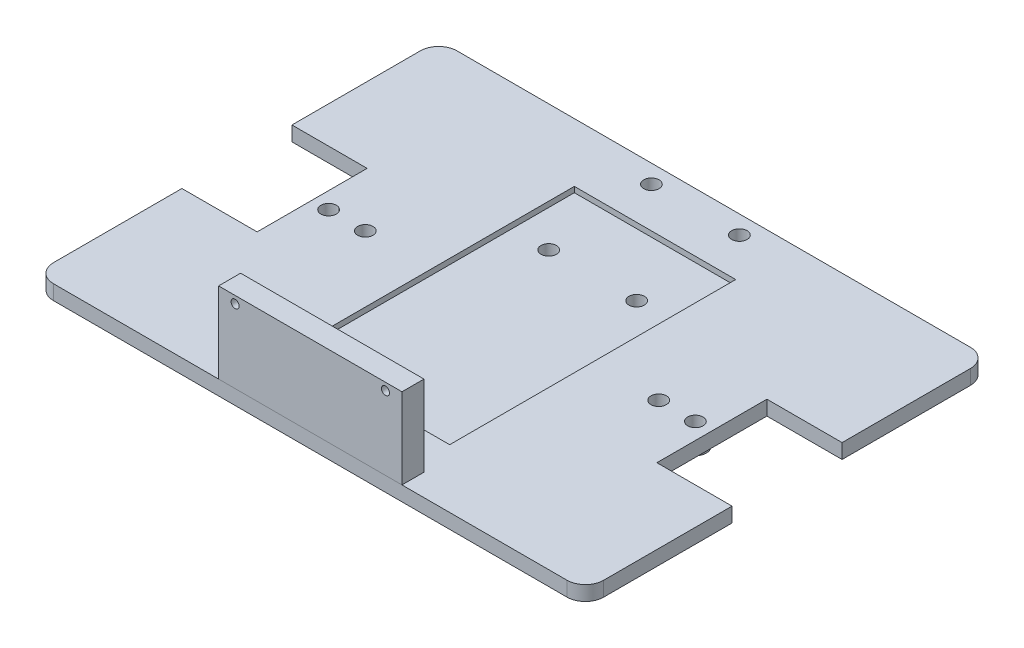
SolidWorks part; units mm, degrees
ref_plane "Front Plane" through (0, 0, 0) normal (0, 0, 1) x (1, 0, 0)
ref_plane "Top Plane" through (0, 0, 0) normal (0, 1, 0) x (1, 0, 0)
ref_plane "Right Plane" through (0, 0, 0) normal (1, 0, 0) x (0, 0, -1)
sketch "Sketch1" plane through (0, 0, 0) normal (0, 1, 0) x (1, 0, 0)
  line L0 (-75, 0) -> (75, 0) construction
  line L1 (-75, -55) -> (75, -55)
  line L2 (-75, -55) -> (-75, 55)
  line L3 (-75, 55) -> (75, 55)
  line L4 (75, -55) -> (75, 55)
  line L5 (-75, -55) -> (75, 55) construction
  line L6 (-75, 55) -> (75, -55) construction
  point P0 (0, 0)
  dimension "D1" = 150
  dimension "D2" = 110
extrude "Boss-Extrude1" add sketch "Sketch1" along normal blind 4
fillet "Fillet1" radius 5 4 edges at (-75, 2, -55) (-75, 2, 55) (75, 2, -55) (75, 2, 55)
sketch "Sketch2" plane through (0, 4, 0) normal (0, 1, 0) x (1, 0, 0)
  line L0 (-75, 0) -> (75, 0) construction
  line L1 (-75, 50) -> (-75, -50) construction
  line L2 (75, -50) -> (75, 50) construction
  line L3 (0, 55) -> (0, -55) construction
  line L4 (70, 55) -> (-70, 55) construction
  line L5 (-70, -55) -> (70, -55) construction
  circle A0 centre (-50, 0) radius 2.1
  circle A1 centre (-40, 0) radius 2.1
  dimension "D1" = 4.2
  dimension "D2" = 50
  dimension "D3" = 4.2
  dimension "D4" = 40
extrude "Cut-Extrude1" cut sketch "Sketch2" against normal through all
sketch "Sketch3" plane through (0, 0, 0) normal (0, -1, 0) x (1, 0, 0)
  line L0 (-75, 0) -> (75, 0) construction
  line L1 (-75, -50) -> (-75, 50) construction
  line L2 (75, 50) -> (75, -50) construction
  line L3 (0, 55) -> (0, -55) construction
  line L4 (-70, 55) -> (70, 55) construction
  line L5 (70, -55) -> (-70, -55) construction
  circle A0 centre (-50, 0) radius 3
  circle A1 centre (-40, 0) radius 3
  dimension "D1" = 6
  dimension "D2" = 6
extrude "Boss-Extrude2" add sketch "Sketch3" along normal blind 2
mirror "Mirror1" about plane through (0, 0, 0) normal (1, 0, 0) of "Boss-Extrude2", "Cut-Extrude1"
sketch "Sketch4" plane through (0, 4, 0) normal (0, 1, 0) x (1, 0, 0)
  line L0 (0, -55) -> (0, 55) construction
  line L1 (-22, -39) -> (-6, -39)
  line L2 (-22, -39) -> (-22, 39)
  line L3 (-22, 39) -> (22, 39)
  line L4 (22, -39) -> (22, 39)
  line L5 (-22, -39) -> (22, 39) construction
  line L6 (-22, 39) -> (22, -39) construction
  line L7 (-70, -55) -> (70, -55) construction
  line L8 (70, 55) -> (-70, 55) construction
  line L9 (6, -39) -> (22, -39)
  line L10 (-6, -43) -> (6, -43)
  line L11 (-6, -43) -> (-6, -39)
  line L13 (6, -43) -> (6, -39)
  line L14 (-6, -43) -> (6, -39) construction
  line L15 (-6, -39) -> (6, -43) construction
  point P0 (0, 0)
  point P15 (0, -41)
  dimension "D1" = 44
  dimension "D2" = 78
  dimension "D3" = 0
  dimension "D4" = 4
  dimension "D5" = 12
extrude "Cut-Extrude2" cut sketch "Sketch4" against normal blind 1.5
sketch "Sketch7" plane through (0, 0, 55) normal (0, 0, 1) x (1, 0, 0)
  line L0 (-70, 4) -> (70, 4) construction
  line L1 (-25, 4) -> (25, 4)
  line L2 (-25, 4) -> (-25, 26)
  line L3 (-25, 26) -> (25, 26)
  line L4 (25, 4) -> (25, 26)
  line L5 (-25, 4) -> (25, 26) construction
  line L6 (-25, 26) -> (25, 4) construction
  line L7 (70, 0) -> (70, 4) construction
  point P0 (0, 4)
  point P10 (0, 26)
  dimension "D1" = 50
  dimension "D2" = 22
  dimension "D3" = 45
extrude "Boss-Extrude4" add sketch "Sketch7" against normal blind 6 separate body
sketch "Sketch8" plane through (0, 0, 49) normal (0, 0, -1) x (-1, 0, 0)
  line L0 (0, 4) -> (0, 26) construction
  line L1 (25, 4) -> (-25, 4) construction
  line L2 (-25, 26) -> (25, 26) construction
  circle A0 centre (-20.5, 24) radius 1.1
  circle A1 centre (20.5, 24) radius 1.1
  dimension "D1" = 2.2
  dimension "D2" = 20.5
  dimension "D3" = 20
extrude "Cut-Extrude3" cut sketch "Sketch8" against normal through all
sketch "Sketch10" plane through (0, 4, 0) normal (0, 1, 0) x (1, 0, 0)
  circle A0 centre (-50, 0) radius 2.1
  circle A1 centre (-40, 0) radius 2.1
  circle A2 centre (40, 0) radius 2.1
  circle A3 centre (50, 0) radius 2.1
  dimension "D1" = 4.2
  dimension "D2" = 4.2
  dimension "D3" = 4.2
  dimension "D4" = 4.2
extrude "Cut-Extrude5" cut sketch "Sketch10" against normal through all
sketch "Sketch11" plane through (0, 4, 0) normal (0, 1, 0) x (1, 0, 0)
  line L0 (75, -50) -> (75, 50) construction
  line L1 (54.5, -15) -> (75, -15)
  line L2 (54.5, -15) -> (54.5, 15)
  line L3 (54.5, 15) -> (75, 15)
  line L4 (75, -15) -> (75, 15)
  line L5 (54.5, -15) -> (75, 15) construction
  line L6 (54.5, 15) -> (75, -15) construction
  line L7 (0, -15.4) -> (0, 15.4) construction
  line L8 (-54.5, 15) -> (-75, -15) construction
  line L9 (-54.5, -15) -> (-75, 15) construction
  line L10 (-75, -15) -> (-75, 15)
  line L11 (-54.5, 15) -> (-75, 15)
  line L12 (-54.5, -15) -> (-54.5, 15)
  line L13 (-54.5, -15) -> (-75, -15)
  point P0 (64.75, 0)
  point P14 (-64.75, 0)
  dimension "D1" = 54.5
  dimension "D2" = 15
  dimension "D3" = 15
extrude "Cut-Extrude6" cut sketch "Sketch11" against normal through all
sketch "Sketch12" plane through (0, 0, 0) normal (0, -1, 0) x (1, 0, 0)
  line L0 (70, -55) -> (-70, -55) construction
  line L1 (-12, -50) -> (12, -50) construction
  line L2 (-12, -50) -> (-12, -22) construction
  line L3 (-12, -22) -> (12, -22) construction
  line L4 (12, -50) -> (12, -22) construction
  line L5 (-12, -50) -> (12, -22) construction
  line L6 (-12, -22) -> (12, -50) construction
  circle A0 centre (-12, -22) radius 4
  circle A1 centre (12, -22) radius 4
  circle A2 centre (12, -50) radius 4
  circle A3 centre (-12, -50) radius 4
  point P0 (0, -36)
  dimension "D4" = 8
  dimension "D1" = 24
  dimension "D2" = 28
  dimension "D3" = 5
extrude "Boss-Extrude5" add sketch "Sketch12" along normal blind 3.5
sketch "Sketch13" plane through (0, 4, 0) normal (0, 1, 0) x (1, 0, 0)
  circle A0 centre (12, 22) radius 2.1
  circle A4 centre (-12, 50) radius 2.1
  circle A6 centre (12, 50) radius 2.1
  circle A7 centre (-12, 22) radius 2.1
  dimension "D1" = 4.2
  dimension "D2" = 4.2
  dimension "D3" = 4.2
  dimension "D4" = 4.2
extrude "Cut-Extrude7" cut sketch "Sketch13" against normal through all
